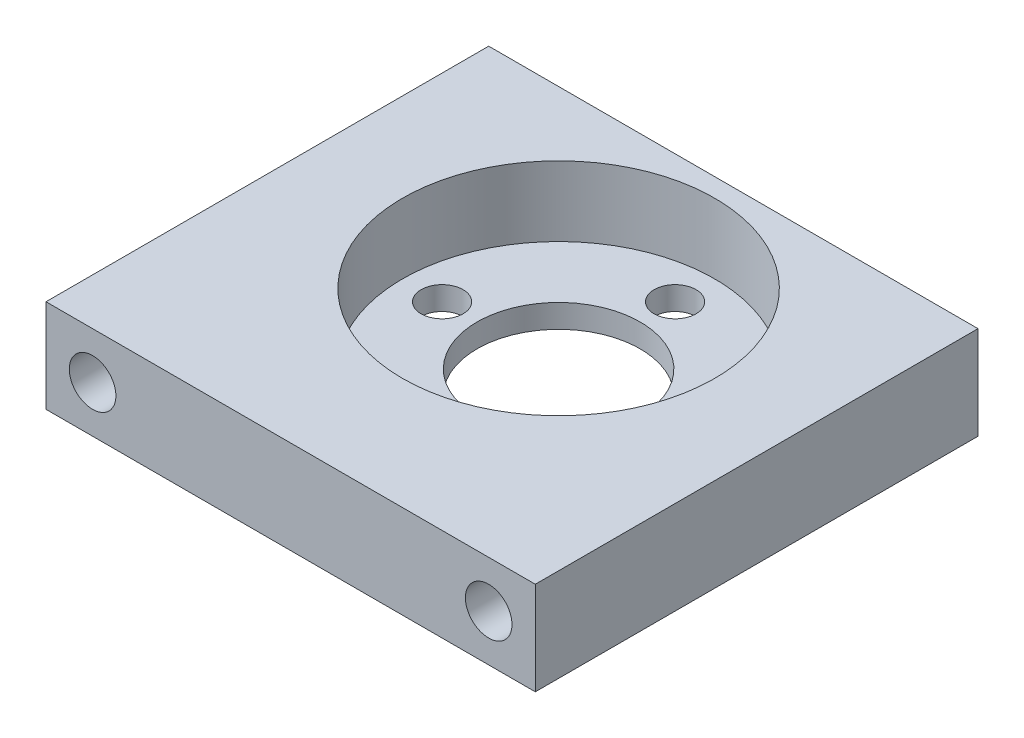
SolidWorks part; units mm, degrees
material "Alliage 1060"
ref_plane "Plan de face" through (0, 0, 0) normal (0, 0, 1) x (1, 0, 0)
ref_plane "Plan de dessus" through (0, 0, 0) normal (0, 1, 0) x (1, 0, 0)
ref_plane "Plan de droite" through (0, 0, 0) normal (1, 0, 0) x (0, 0, -1)
sketch "Esquisse1" plane through (0, 0, 0) normal (0, 1, 0) x (1, 0, 0)
  line L1 (0, 0) -> (42, 0)
  line L2 (0, 0) -> (0, 46)
  line L3 (0, 46) -> (42, 46)
  line L4 (42, 0) -> (42, 46)
  dimension "D1" = 42
  dimension "D2" = 46
extrude "Boss.-Extru.1" add sketch "Esquisse1" along normal blind 8
sketch "Esquisse2" plane through (0, 8, 0) normal (0, 1, 0) x (1, 0, 0)
  line L2 (0, 23) -> (42, 23) construction
  line L3 (0, 46) -> (0, 0) construction
  line L4 (42, 0) -> (42, 46) construction
  circle A0 centre (21, 23) radius 13.4
  point P9 (21, 23)
  dimension "D1" = 26.8
extrude "Enlèv. mat.-Extru.1" cut sketch "Esquisse2" against normal blind 6
sketch "Esquisse3" plane through (0, 2, 0) normal (0, 1, 0) x (1, 0, 0)
  line L0 (21, 23) -> (21, 33) construction
  circle A0 centre (21, 23) radius 7
  circle A1 centre (21, 33) radius 1.8
  circle A2 centre (31, 23) radius 1.8
  circle A3 centre (21, 13) radius 1.8
  circle A4 centre (11, 23) radius 1.8
  point P14 (21, 23)
  dimension "D1" = 14
  dimension "D3" = 3.6
  dimension "D2" = 10
  dimension "D4" = 4
extrude "Enlèv. mat.-Extru.2" cut sketch "Esquisse3" against normal through all
sketch "Esquisse4" plane through (0, 0, -46) normal (0, 0, -1) x (-1, 0, 0)
  line L0 (-42, 4) -> (0, 4) construction
  line L1 (-42, 8) -> (-42, 0) construction
  line L2 (0, 8) -> (0, 0) construction
  circle A0 centre (-38, 4) radius 2
  circle A1 centre (-4, 4) radius 2
  dimension "D1" = 4
  dimension "D2" = 4
  dimension "D3" = 4
extrude "Enlèv. mat.-Extru.3" cut sketch "Esquisse4" against normal through all
sketch "Esquisse5" plane through (0, 8, 0) normal (0, 1, 0) x (1, 0, 0)
  line L0 (42, 0) -> (42, 46) construction
  line L1 (0, 46) -> (42, 46)
  line L2 (0, 46) -> (0, 38)
  line L3 (0, 38) -> (42, 38)
  line L4 (42, 46) -> (42, 38)
  dimension "D1" = 8
extrude "Enlèv. mat.-Extru.4" cut sketch "Esquisse5" against normal up to next
